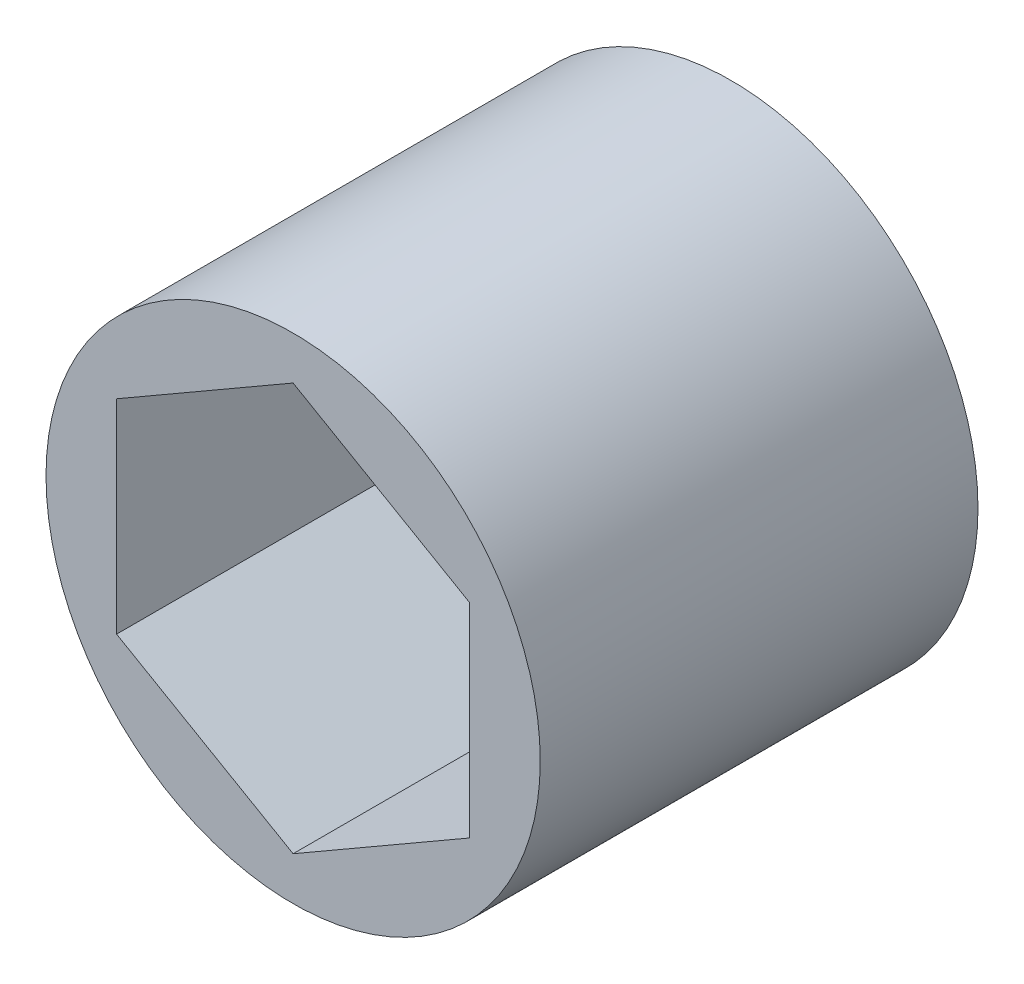
SolidWorks part; units mm, degrees
material "PET"
ref_plane "Front Plane" through (0, 0, 0) normal (0, 0, 1) x (1, 0, 0)
ref_plane "Top Plane" through (0, 0, 0) normal (0, 1, 0) x (1, 0, 0)
ref_plane "Right Plane" through (0, 0, 0) normal (1, 0, 0) x (0, 0, -1)
sketch "Sketch1" plane through (0, 0, 0) normal (0, 0, 1) x (1, 0, 0)
  line L1 (0, 7.3323) -> (-6.35, 3.6662)
  line L2 (-6.35, 3.6662) -> (-6.35, -3.6662)
  line L3 (-6.35, -3.6662) -> (0, -7.3323)
  line L4 (0, -7.3323) -> (6.35, -3.6662)
  line L5 (6.35, -3.6662) -> (6.35, 3.6662)
  line L6 (6.35, 3.6662) -> (0, 7.3323)
  circle A0 centre (0, 0) radius 8.89
  circle A1 centre (0, 0) radius 6.35 construction
  dimension "D1" = 12.7
  dimension "D2" = 17.78
extrude "Boss-Extrude1" add sketch "Sketch1" along normal mid plane 15.748
